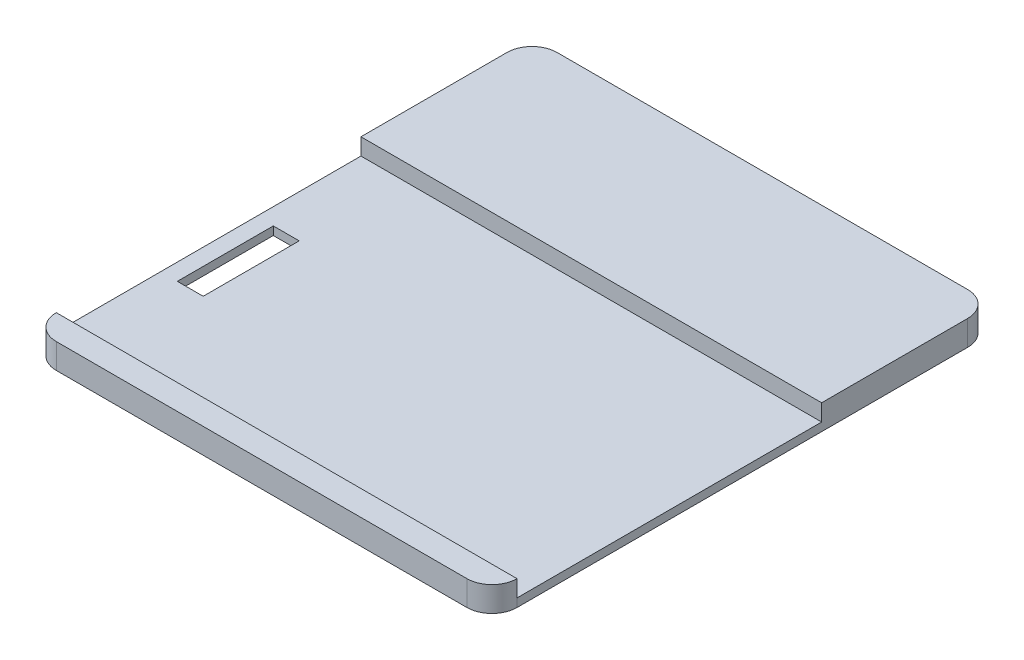
SolidWorks part; units mm, degrees
material "PMMA"
ref_plane "Front Plane" through (0, 0, 0) normal (0, 0, 1) x (1, 0, 0)
ref_plane "Top Plane" through (0, 0, 0) normal (0, 1, 0) x (1, 0, 0)
ref_plane "Right Plane" through (0, 0, 0) normal (1, 0, 0) x (0, 0, -1)
sketch "Sketch1" plane through (0, 0, 0) normal (0, 1, 0) x (1, 0, 0)
  line L0 (0, 51.4541) -> (0, -51.759) construction
  line L1 (-52.1402, 0) -> (52.1402, 0) construction
  line L2 (0, -8.75) -> (25.0802, -8.75) construction
  line L3 (-24.6, -30) -> (24.6, -30)
  line L4 (-27.6, -27) -> (-27.6, 27)
  line L5 (-24.6, 30) -> (24.6, 30)
  line L6 (27.6, -27) -> (27.6, 27)
  line L7 (-27.6, -30) -> (27.6, 30) construction
  line L8 (-27.6, 30) -> (27.6, -30) construction
  line L9 (-27.6, -27) -> (27.6, -27)
  line L10 (-27.6, -27) -> (-27.6, 9.5)
  line L11 (-27.6, 9.5) -> (27.6, 9.5)
  line L12 (27.6, -27) -> (27.6, 9.5)
  line L13 (-27.6, -27) -> (27.6, 9.5) construction
  line L14 (-27.6, 9.5) -> (27.6, -27) construction
  line L18 (-22.5, -3) -> (-25.6, -3)
  line L19 (-22.5, -3) -> (-22.5, -14.5)
  line L20 (-22.5, -14.5) -> (-25.6, -14.5)
  line L21 (-25.6, -3) -> (-25.6, -14.5)
  arc A0 (27.6, 27) -> (24.6, 30) centre (24.6, 27) ccw
  arc A1 (27.6, -27) -> (24.6, -30) centre (24.6, -27) cw
  arc A2 (-24.6, -30) -> (-27.6, -27) centre (-24.6, -27) cw
  arc A3 (-24.6, 30) -> (-27.6, 27) centre (-24.6, 27) ccw
  point P5 (0, 0)
  point P11 (0, -8.75)
  dimension "D10" = 3
  dimension "D1" = 60
  dimension "D2" = 55.2
  dimension "D3" = 55.2
  dimension "D4" = 36.5
  dimension "D5" = 3
  dimension "D6" = 11.5
  dimension "D7" = 3.1
  dimension "D8" = 2
  dimension "D9" = 3
extrude "Boss-Extrude1" add sketch "Sketch1" along normal blind 3 contours A2 L3 A1 L9 | L5 A3 L4 L11 L6 A0 region at (0, 0, 28.4802) region at (0, 0, -19.7172)
extrude "Boss-Extrude2" add sketch "Sketch1<5>" along normal blind 1 contours L11 L4 L9 L6 L21 L18 L19 L20 region at (0.4332, 0, 8.75)
sketch "Sketch1<5>" plane through (0, 0, 0) normal (0, 1, 0) x (1, 0, 0) same geometry as "Sketch1"
